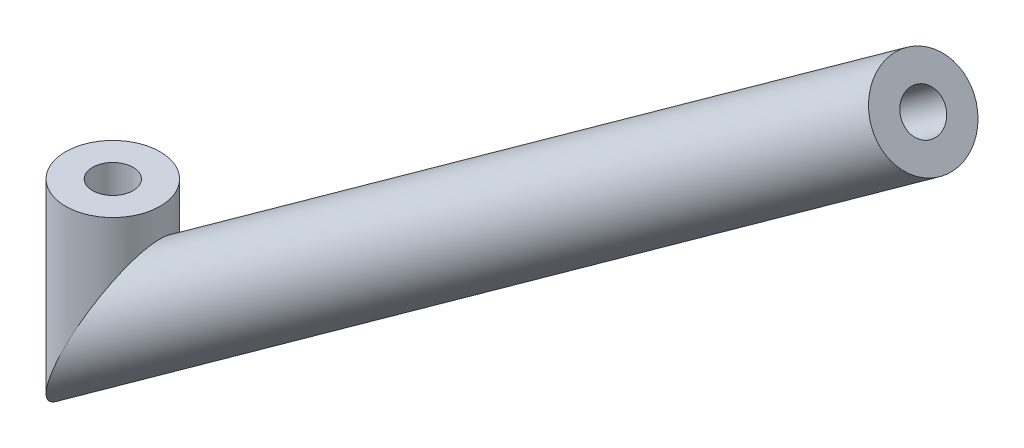
SolidWorks part; units mm, degrees
ref_plane "Front Plane" through (0, 0, 0) normal (0, 0, 1) x (1, 0, 0)
ref_plane "Top Plane" through (0, 0, 0) normal (0, 1, 0) x (1, 0, 0)
ref_plane "Right Plane" through (0, 0, 0) normal (1, 0, 0) x (0, 0, -1)
sketch "Sketch7" plane through (0, 0, 0) normal (0, 0, 1) x (1, 0, 0)
  line L0 (0.1791, 11.0727) -> (60.202, 54.3067)
  line L1 (0.1791, 11.0727) -> (0.1791, 20)
  point P3 (43.7002, 0)
  point P5 (34.0921, 19.2367)
  point P6 (45.9615, 42.7946)
  point P7 (47.4533, 43.4889)
  point P8 (48.1261, 42.9846)
  point P9 (52.6246, 48.4296)
  point P10 (60.202, 54.3067)
  point P11 (0.1791, 11.0727)
sweep "Sweep-Thin1" add path "Sketch7" circular profile diameter 3 parameters "D1"=2, "D3"=3
ref_plane "Plane2" through (0, -2, 0) normal (0, -1, 0) x (-1, 0, 0)
equation "\"3.00mmmm\"=3"
